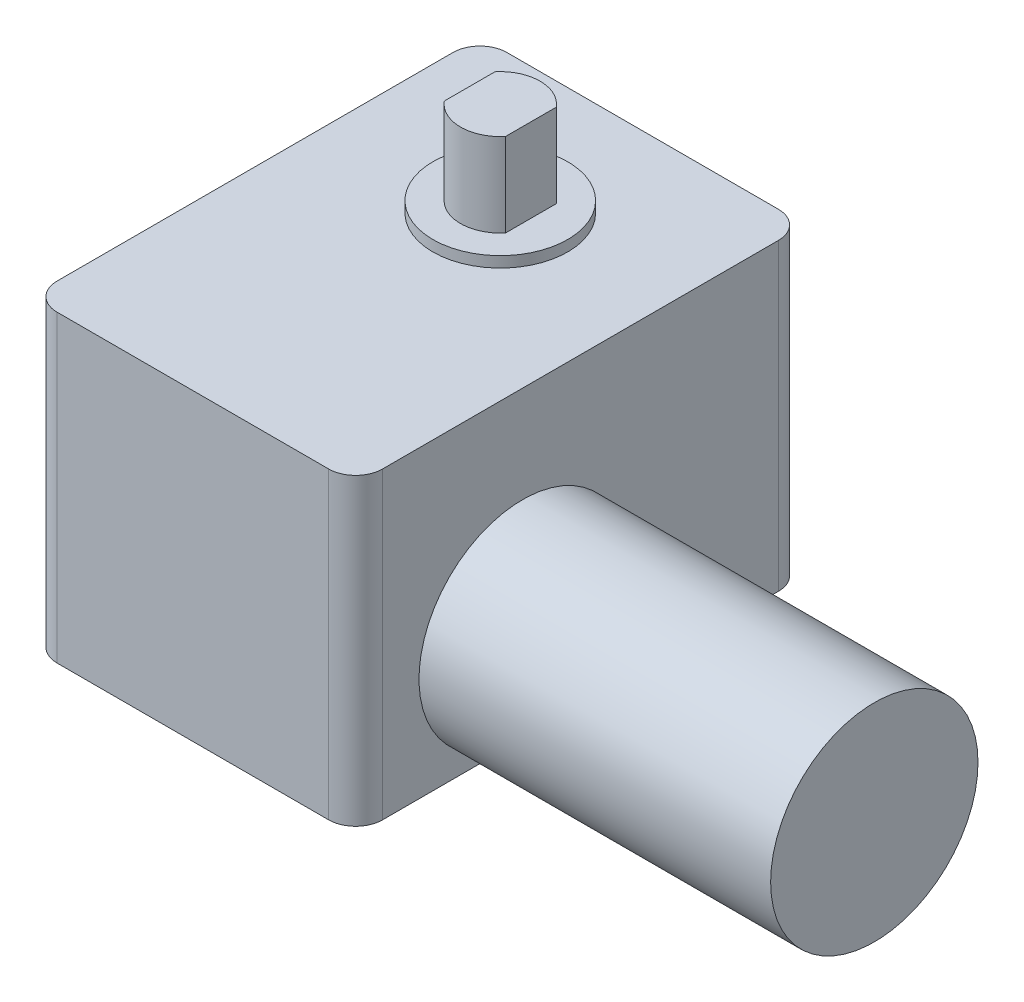
SolidWorks part; units mm, degrees
material "Delrin 2700 NC010, Low Viscosity Acetal Copolymer (SS)"
ref_plane "Front Plane" through (0, 0, 0) normal (0, 0, 1) x (1, 0, 0)
ref_plane "Top Plane" through (0, 0, 0) normal (0, 1, 0) x (1, 0, 0)
ref_plane "Right Plane" through (0, 0, 0) normal (1, 0, 0) x (0, 0, -1)
sketch "Sketch2" plane through (0, 0, 0) normal (0, 1, 0) x (1, 0, 0)
  line L0 (0, 0) -> (0, 16.68)
  line L1 (0, 0) -> (12.07, 0)
  line L2 (0, 16.68) -> (12.07, 16.68)
  line L3 (12.07, 0) -> (12.07, 16.68)
  line L4 (12.07, 2.35) -> (12.07, 10.04)
  line L5 (12.07, 2.35) -> (25.11, 2.35)
  line L7 (25.11, 2.35) -> (25.11, 6.195)
  line L8 (4.8983, 12.34) -> (4.8983, 10.46)
  line L9 (7.1717, 12.34) -> (7.1717, 10.46)
  line L10 (25.11, 6.195) -> (12.07, 6.195)
  circle A0 centre (6.035, 11.4) radius 2.5
  arc A1 (4.8983, 10.46) -> (7.1717, 10.46) centre (6.035, 11.4) ccw
  arc A2 (7.1717, 12.34) -> (4.8983, 12.34) centre (6.035, 11.4) ccw
  point P11 (6.035, 16.68)
  dimension "D7" = 5
  dimension "D8" = 2.95
  dimension "D1" = 12.07
  dimension "D2" = 16.68
  dimension "D3" = 2.35
  dimension "D4" = 3.845
  dimension "D5" = 25.11
  dimension "D6" = 11.4
  dimension "D9" = 1.88
revolve "Revolve1" add sketch "Sketch2" angle 360 about L10 region at (18.59, 0, -4.2725)
extrude "Boss-Extrude1" add sketch "Sketch2<5>" against normal blind 3.845 contours L1 L3 L4 L2 L0 A0 | A0 A2 L9 A1 L8 | L9 A2 L8 A1 region at (6.035, 0, -8.0093) region at (6.035, 0, -11.4) region at (3.6057, 0, -11.4)
sketch "Sketch2<5>" plane through (0, 0, 0) normal (0, 1, 0) x (1, 0, 0) same geometry as "Sketch2"
extrude "Boss-Extrude2" add sketch "Sketch2<6>" along normal blind 7.425 contours L1 L3 L4 L2 L0 A0 region at (6.035, 0, -8.0093)
sketch "Sketch2<6>" plane through (0, 0, 0) normal (0, 1, 0) x (1, 0, 0) same geometry as "Sketch2"
extrude "Boss-Extrude3" add sketch "Sketch2<7>" along normal blind 7.825 contours A0 A2 L9 A1 L8 region at (3.6057, 0, -11.4)
sketch "Sketch2<7>" plane through (0, 0, 0) normal (0, 1, 0) x (1, 0, 0) same geometry as "Sketch2"
extrude "Boss-Extrude4" add sketch "Sketch2<8>" along normal blind 10.925 contours L9 A2 L8 A1 region at (6.035, 0, -11.4)
sketch "Sketch2<8>" plane through (0, 0, 0) normal (0, 1, 0) x (1, 0, 0) same geometry as "Sketch2"
fillet "Fillet1" radius 1 4 edges at (0, 1.79, 0) (12.07, 1.79, 0) (12.07, 1.79, -16.68) (0, 1.79, -16.68)
equation "\"whitemotordepth\"=11.27mm"
equation "\"D1@Boss-Extrude2\"=\"whitemotordepth\" - \"whitemotorbackdepth\""
equation "\"whitemotorbackdepth\"=3.845mm"
equation "\"D1@Boss-Extrude1\"=\"whitemotorbackdepth\""
equation "\"D1@Boss-Extrude3\"=\"whitemotordepth\"-\"whitemotorbackdepth\"+.4"
equation "\"whitemotoraxledepth\" = 3.5mm"
equation "\"D1@Boss-Extrude4\"=\"whitemotoraxledepth\"+\"whitemotordepth\"-\"whitemotorbackdepth\""
equation "\"whitemotoraxleoffset\"=11.4mm"
equation "\"D6@Sketch2\"=\"whitemotoraxleoffset\""
equation "\"whitemotorwidth\"=12.07mm"
equation "\"D1@Sketch2\"=\"whitemotorwidth\""
equation "\"whitemotorheight\"=16.68mm"
equation "\"D2@Sketch2\"=\"whitemotorheight\""
equation "\"whitemotorcylinderlength\" =13.04mm"
equation "\"D5@Sketch2\"=\"whitemotorcylinderlength\"+\"whitemotorwidth\""
equation "\"whitemotorcylinderradius\"=3.845mm"
equation "\"D4@Sketch2\"=\"whitemotorcylinderradius\""
equation "\"whitemotorcylinderoffset\"=2.35mm"
equation "\"D3@Sketch2\"=\"whitemotorcylinderoffset\""
equation "\"whitemotorcutoutlength\"=1.88mm"
equation "\"D9@Sketch2\"=\"whitemotorcutoutlength\""
equation "\"whitemotorouterrad\"=5mm"
equation "\"D7@Sketch2\"=\"whitemotorouterrad\""
equation "\"whitemotorinnerrad\"=2.95mm"
equation "\"D8@Sketch2\"=\"whitemotorinnerrad\""
equation "\"CageLeftBottomEdge\"=22.11mm"
equation "\"CageLeftTopEdge\"=22.11mm"
equation "\"CageRightBottomEdge\"=21.63mm"
equation "\"CageRightTopEdge\"=21.63mm"
equation "\"CageHeight\"=86.04mm"
equation "\"CageLength\"=73.76mm"
equation "\"CageTopScrewClearance\"=10mm"
equation "\"CageBottomScrewClearance\"=25mm"
equation "\"CageLeftTopDepth\"= 11.65mm"
equation "\"CageLeftBottomDepth\"=11.11mm"
equation "\"CageLeftTopHeight\"=8.56175mm"
equation "\"CageLeftBottomHeight\"=16mm"
equation "\"CageRightTopDepth\"= 11.05mm"
equation "\"CageRightBottomDepth\"=10.58mm"
equation "\"CageRightTopHeight\"=9.6mm"
equation "\"CageRightBottomHeight\"=15.49mm"
equation "\"CageLeftTopChannelDepth\"=2.41908mm"
equation "\"CageLeftBottomChannelDepth\"=2.588mm"
equation "\"CageLeftChannelHeight\"=11.7mm"
equation "\"CageRightTopChannelDepth\"=2.32mm"
equation "\"CageRightBottomChannelDepth\"=2.318mm"
equation "\"CageRightChannelHeight\"=10mm"
equation "\"CageChanRelHeight\"=23.99mm"
equation "\"CageChanRelDepth\"=5.492mm"
equation "\"CageChamberRadius\"=16.261mm"
equation "\"CageScrewDiameter\"=4.8mm"
equation "\"CageSetScrewDiameter\"=3.5mm"
equation "\"CageAxleRadius\"=6.639mm"
equation "\"CageAxleKeyHeight\"=1.619mm"
equation "\"CageAxleKeyWidth\"=2.662mm"
equation "\"CageHoseWindowWidth\"=16.29mm"
equation "\"CageHoseWindowHeight\"=26.5mm"
equation "\"CageHoseWindow-Edge\"=8.89mm"
equation "\"CageScrew-VerticalEdge\"=5.0mm"
equation "\"CageScrew-HorizontalEdge\"=7.5mm"
equation "\"CageScrew-HoseCornerScrewEdge\"=4.45mm"
equation "\"CageAxle-BottomEdge\"=56.05mm"
equation "\"CageAxle-FrontEdge\"=46.03mm"
equation "\"CageBackSetScrew-Axle\"=40mm"
equation "\"CageFrontSetScrew-Axle\"=22mm"
equation "\"CageVelocityWindow-BackEdge\"=34.8mm"
equation "\"CageVelocityWindow-BottomEdge\"=27.55mm"
equation "\"CageVelocityWindowHeight\"=22.29mm"
equation "\"CageVelocityWindowWidth\"=12.61mm"
equation "\"TriggerSlot-BottomEdge\"=6.35mm"
equation "\"TriggerSlot-FrontEdge\"=15mm"
equation "\"TriggerSlotSize\"=6.7mm"
equation "\"vigorwidth\"= 0.472441in"
equation "\"vigorflangewidth\"= 0.731102in"
equation "\"vigorflangelength\"= 0.131102in"
equation "\"vigorscrewsize\"= 0.066535in"
equation "\"vigorholeoffsetwid\"= 0.0646653in"
equation "\"vigorholeoffsetlen\"= 0.065551in"
equation "\"vigorflangedepth\"= 0.0901575in"
equation "\"vigordiscdepth\"= 0.0492126in"
equation "\"vigormotordepth\"= 1.12362in"
equation "\"vigortipdepth\"= 0.259055in"
equation "\"vigoraxlewidth\"= 0.173622in"
equation "\"vigorcutlen\"= 0.0480315in"
equation "\"vigoraxledepth\"= 0.159055in"
equation "\"TriggerRackOffset\"=.236224in"
equation "\"TriggerSlotSizeInt\"=.25in"
equation "\"MotorMountLegLength\"=.25in"
equation "\"GearOffset\"=.264907in"
equation "\"TriggerSlotSpacing\"=.25in"
equation "\"TGMGearFaceDiameter\"=24.40mm"
equation "\"TGMCylinderLength\"=15.00mm"
equation "\"TGMScrewHole-Center\"=8.70mm"
equation "\"TGMScrewHoleDiameter\"=5.04mm"
equation "\"TGMCenterHoleDiameter\"=9.50mm"
equation "\"TGMShaftCollarSideLength\"=19.00mm"
equation "\"TGMShaftCollarDockingDepth\"=7.00mm"
